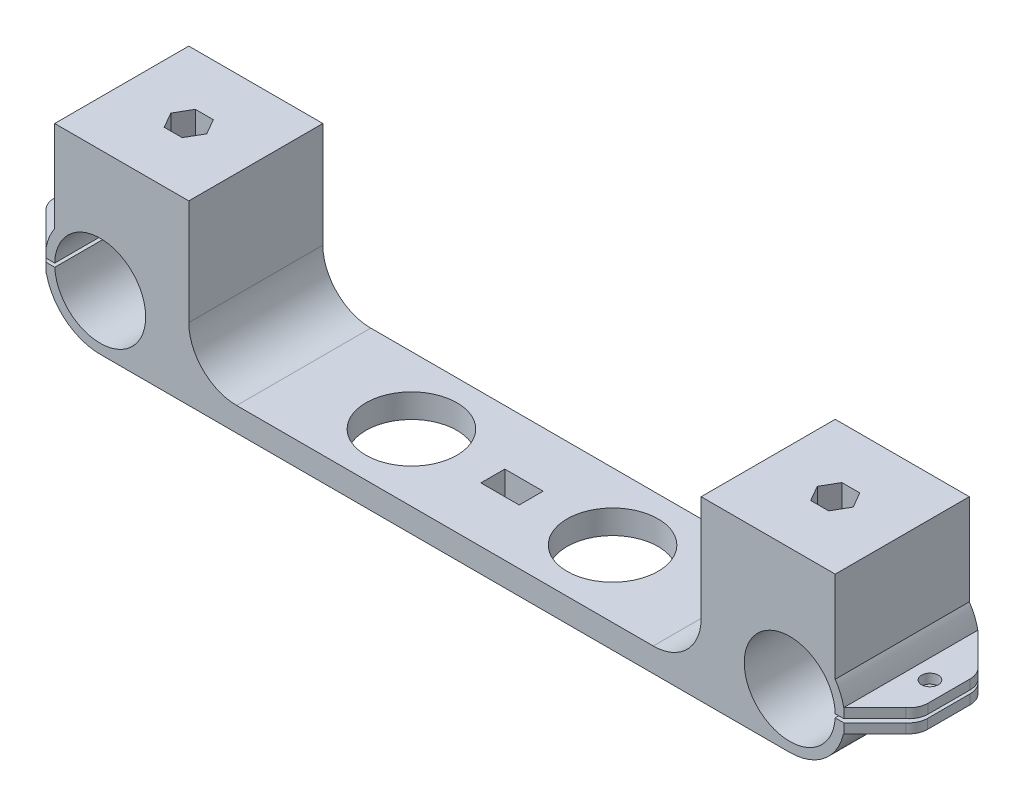
SolidWorks part; units mm, degrees
ref_plane "Front Plane" through (0, 0, 0) normal (0, 0, 1) x (1, 0, 0)
ref_plane "Top Plane" through (0, 0, 0) normal (0, 1, 0) x (1, 0, 0)
ref_plane "Right Plane" through (0, 0, 0) normal (1, 0, 0) x (0, 0, -1)
sketch "Sketch7" plane through (0, 0, 0) normal (0, 0, 1) x (1, 0, 0)
  line L0 (-29.0094, -3.6853) -> (114.9906, -3.6853)
  line L1 (-10.5061, 1.3147) -> (96.4873, 1.3147)
  line L2 (126.2156, 5.3147) -> (134.2156, 5.3147)
  line L3 (134.2156, 5.3147) -> (134.2156, 7.3147)
  line L4 (134.2156, 7.3147) -> (126.4797, 7.3147)
  line L5 (126.4879, 8.0647) -> (134.2683, 8.0647)
  line L6 (134.2683, 8.0647) -> (134.2683, 10.0647)
  line L7 (134.2683, 10.0647) -> (126.2683, 10.0647)
  line L8 (126.4797, 7.3147) -> (124.4774, 7.3147)
  line L9 (126.4879, 8.0647) -> (124.4873, 8.0647)
  line L10 (42.9906, -3.6853) -> (42.9906, 54.826) construction
  line L11 (-40.5067, 8.0647) -> (-38.5061, 8.0647)
  line L12 (-40.4985, 7.3147) -> (-38.4962, 7.3147)
  line L13 (-40.2344, 5.3147) -> (-48.2344, 5.3147)
  line L14 (-48.2344, 7.3147) -> (-40.4985, 7.3147)
  line L15 (-48.2344, 5.3147) -> (-48.2344, 7.3147)
  line L16 (-48.2872, 8.0647) -> (-48.2872, 10.0647)
  line L17 (-40.5067, 8.0647) -> (-48.2872, 8.0647)
  line L18 (-48.2872, 10.0647) -> (-40.2872, 10.0647)
  line L19 (-38.5061, 14.3003) -> (-38.5061, 33.3147)
  line L20 (-38.5061, 33.3147) -> (-10.5061, 33.3147)
  line L21 (-10.5061, 33.3147) -> (-10.5061, 1.3147)
  line L22 (96.4873, 33.3147) -> (96.4873, 1.3147)
  line L23 (124.4873, 14.3003) -> (124.4873, 33.3147)
  line L24 (124.4873, 33.3147) -> (96.4873, 33.3147)
  arc A0 (124.4873, 8.0647) -> (124.4774, 7.3147) centre (114.9906, 7.8147) ccw
  arc A1 (-38.4962, 7.3147) -> (-38.5061, 8.0647) centre (-29.0094, 7.8147) ccw
  arc A2 (114.9906, -3.6853) -> (126.2156, 5.3147) centre (114.9906, 7.8147) ccw
  arc A3 (-38.5061, 14.3003) -> (-40.2872, 10.0647) centre (-29.0094, 7.8147) ccw
  arc A4 (-40.2344, 5.3147) -> (-29.0094, -3.6853) centre (-29.0094, 7.8147) ccw
  arc A6 (126.2683, 10.0647) -> (124.4873, 14.3003) centre (114.9906, 7.8147) ccw
  dimension "D2" = 19
  dimension "D3" = 23
  dimension "D11" = 28
  dimension "D1" = 144
  dimension "D4" = 5
  dimension "D5" = 2
  dimension "D6" = 2
  dimension "D7" = 0.75
  dimension "D8" = 0.5
  dimension "D9" = 8
  dimension "D10" = 8
  dimension "D12" = 32
extrude "Boss-Extrude3" add sketch "Sketch7" along normal blind 28
fillet "Fillet1" radius 10 2 edges at (96.4873, 1.3147, 14) (-10.5061, 1.3147, 14)
sketch "Sketch8" plane through (0, 1.3147, 0) normal (0, 1, 0) x (1, 0, 0)
  line L0 (42.9906, 0) -> (42.9906, -28) construction
  line L1 (86.4873, 0) -> (-0.5061, 0) construction
  line L2 (86.4873, -28) -> (-0.5061, -28) construction
  line L3 (86.4873, -14) -> (-0.5061, -14) construction
  line L4 (38.9906, -11.5) -> (46.9906, -11.5)
  line L5 (38.9906, -11.5) -> (38.9906, -16.5)
  line L6 (38.9906, -16.5) -> (46.9906, -16.5)
  line L7 (46.9906, -11.5) -> (46.9906, -16.5)
  line L8 (86.4873, -28) -> (86.4873, 0) construction
  line L9 (-0.5061, 0) -> (-0.5061, -28) construction
  circle A0 centre (63.9906, -14) radius 9.5
  circle A1 centre (21.9906, -14) radius 9.5
  dimension "D5" = 19
  dimension "D7" = 21
  dimension "D1" = 5
  dimension "D2" = 8
  dimension "D3" = 4
  dimension "D4" = 2.5
  dimension "D6" = 21
extrude "Cut-Extrude4" cut sketch "Sketch8" against normal up to surface (5 mm away) up to face at (42.9906, -3.6853, 14)
sketch "Sketch9" plane through (0, 10.0647, 0) normal (0, 1, 0) x (1, 0, 0)
  line L0 (130.2683, 0) -> (130.2683, -28) construction
  line L1 (134.2683, 0) -> (126.2683, 0) construction
  line L2 (134.2683, -28) -> (126.2683, -28) construction
  line L3 (-44.2872, 0) -> (-44.2872, -28) construction
  line L4 (-40.2872, 0) -> (-48.2872, 0) construction
  line L5 (-40.2872, -28) -> (-48.2872, -28) construction
  circle A0 centre (130.2683, -14) radius 1.75
  circle A3 centre (-44.2872, -14) radius 1.75
  dimension "D1" = 3.5
extrude "Cut-Extrude5" cut sketch "Sketch9" against normal blind 20
sketch "Sketch10" plane through (0, 33.3147, 0) normal (0, 1, 0) x (1, 0, 0)
  line L0 (124.4873, -14) -> (-38.5061, -14) construction
  line L1 (124.4873, -28) -> (124.4873, 0) construction
  line L2 (-38.5061, -28) -> (-38.5061, 0) construction
  line L3 (110.4906, 0) -> (110.4906, -28) construction
  line L4 (124.4873, 0) -> (96.4873, 0) construction
  line L5 (124.4873, -28) -> (96.4873, -28) construction
  line L6 (-24.5094, 0) -> (-24.5094, -28) construction
  line L7 (-10.5061, 0) -> (-38.5061, 0) construction
  line L8 (-10.5061, -28) -> (-38.5061, -28) construction
  line L9 (86.4873, 0) -> (-0.5061, 0) construction
  circle A0 centre (110.4906, -14) radius 1.75
  circle A1 centre (-24.5094, -14) radius 1.75
  point P30 (42.9906, 0)
  dimension "D1" = 3.5
  dimension "D2" = 135
  dimension "D3" = 67.5
extrude "Cut-Extrude6" cut sketch "Sketch10" against normal blind 10
sketch "Sketch12" plane through (0, 10.0647, 0) normal (0, 1, 0) x (1, 0, 0)
  line L0 (130.2683, -21.5) -> (126.2683, -21.5)
  line L1 (126.2683, -28) -> (126.2683, 0) construction
  line L2 (126.2683, -21.5) -> (126.2683, -28)
  line L3 (126.2683, -28) -> (134.2683, -28)
  line L4 (134.2683, -28) -> (134.2683, -21.5)
  line L5 (134.2683, -28) -> (134.2683, 0) construction
  line L6 (134.2683, -21.5) -> (130.2683, -21.5)
  line L7 (130.2683, -6.5) -> (126.2683, -6.5)
  line L8 (126.2683, -6.5) -> (126.2683, 0)
  line L9 (126.2683, 0) -> (134.2683, 0)
  line L10 (134.2683, 0) -> (134.2683, -6.5)
  line L11 (134.2683, -6.5) -> (130.2683, -6.5)
  line L12 (-44.2872, -6.5) -> (-40.2872, -6.5)
  line L13 (-40.2872, -28) -> (-40.2872, 0) construction
  line L14 (-40.2872, -6.5) -> (-40.2872, 0)
  line L15 (-40.2872, 0) -> (-48.2872, 0)
  line L16 (-48.2872, 0) -> (-48.2872, -6.5)
  line L17 (-48.2872, -28) -> (-48.2872, 0) construction
  line L18 (-48.2872, -6.5) -> (-44.2872, -6.5)
  line L19 (-44.2872, -21.5) -> (-48.2872, -21.5)
  line L20 (-48.2872, -21.5) -> (-48.2872, -28)
  line L21 (-48.2872, -28) -> (-40.2872, -28)
  line L22 (-40.2872, -28) -> (-40.2872, -21.5)
  line L23 (-40.2872, -21.5) -> (-44.2872, -21.5)
  circle A0 centre (130.2683, -14) radius 7.5 construction
  circle A1 centre (-44.2872, -14) radius 7.5 construction
  dimension "D1" = 15
extrude "Cut-Extrude8" cut sketch "Sketch12" against normal blind 10
chamfer "Chamfer1" distance 6.5 angle 45 8 edges at (126.2683, 9.0647, 6.5) (126.2683, 6.3147, 6.5) (126.2683, 6.3147, 21.5) (126.2683, 9.0647, 21.5) (-40.2872, 6.3147, 21.5) (-40.2872, 6.3147, 6.5) (-40.2872, 9.0647, 6.5) (-40.2872, 9.0647, 21.5)
fillet "Fillet3" radius 4 8 edges at (134.2683, 9.0647, 21.5) (134.2156, 6.3147, 21.5) (134.2156, 6.3147, 6.5) (134.2683, 9.0647, 6.5) (-48.2344, 6.3147, 6.5) (-48.2344, 6.3147, 21.5) (-48.2872, 9.0647, 21.5) (-48.2872, 9.0647, 6.5)
sketch "Sketch13" plane through (0, 33.3147, 0) normal (0, 1, 0) x (1, 0, 0)
  line L0 (124.4873, -28) -> (96.4873, -28) construction
  line L1 (108.6142, -17.25) -> (112.367, -17.25)
  line L2 (112.367, -17.25) -> (114.2434, -14)
  line L3 (114.2434, -14) -> (112.367, -10.75)
  line L4 (112.367, -10.75) -> (108.6142, -10.75)
  line L5 (108.6142, -10.75) -> (106.7378, -14)
  line L6 (106.7378, -14) -> (108.6142, -17.25)
  line L7 (-20.7566, -14) -> (-22.633, -10.75)
  line L8 (-22.633, -10.75) -> (-26.3858, -10.75)
  line L9 (-26.3858, -10.75) -> (-28.2622, -14)
  line L10 (-28.2622, -14) -> (-26.3858, -17.25)
  line L11 (-26.3858, -17.25) -> (-22.633, -17.25)
  line L12 (-22.633, -17.25) -> (-20.7566, -14)
  circle A0 centre (110.4906, -14) radius 3.25 construction
  circle A1 centre (-24.5094, -14) radius 3.25 construction
  dimension "D1" = 6.5
extrude "Cut-Extrude9" cut sketch "Sketch13" against normal blind 5
sketch "Sketch14" [suppressed] plane through (0, 0, 28) normal (0, 0, 1) x (1, 0, 0)
  line L1 (-82.4893, 23.5071) -> (44.7899, 150.7863)
  line L2 (-82.4893, 23.5071) -> (44.7899, -103.7721)
  line L3 (44.7899, -103.7721) -> (172.0692, 23.5071)
  line L4 (44.7899, 150.7863) -> (172.0692, 23.5071)
  line L6 (124.4774, 32.3147) -> (96.4774, 32.3147) construction
  dimension "D1" = 180
  dimension "D2" = 180
  dimension "D3" = 45
sketch "Sketch11" plane through (0, 0, 28) normal (0, 0, 1) x (1, 0, 0)
  line L1 (-81.97, 61.9449) -> (93.8843, 61.9449)
  line L2 (-81.97, 61.9449) -> (-81.97, -12.8023)
  line L3 (-81.97, -12.8023) -> (93.8843, -12.8023)
  line L4 (93.8843, 61.9449) -> (93.8843, -12.8023)
extrude "Cut-Extrude7" [suppressed] cut sketch "Sketch11" against normal blind 56
